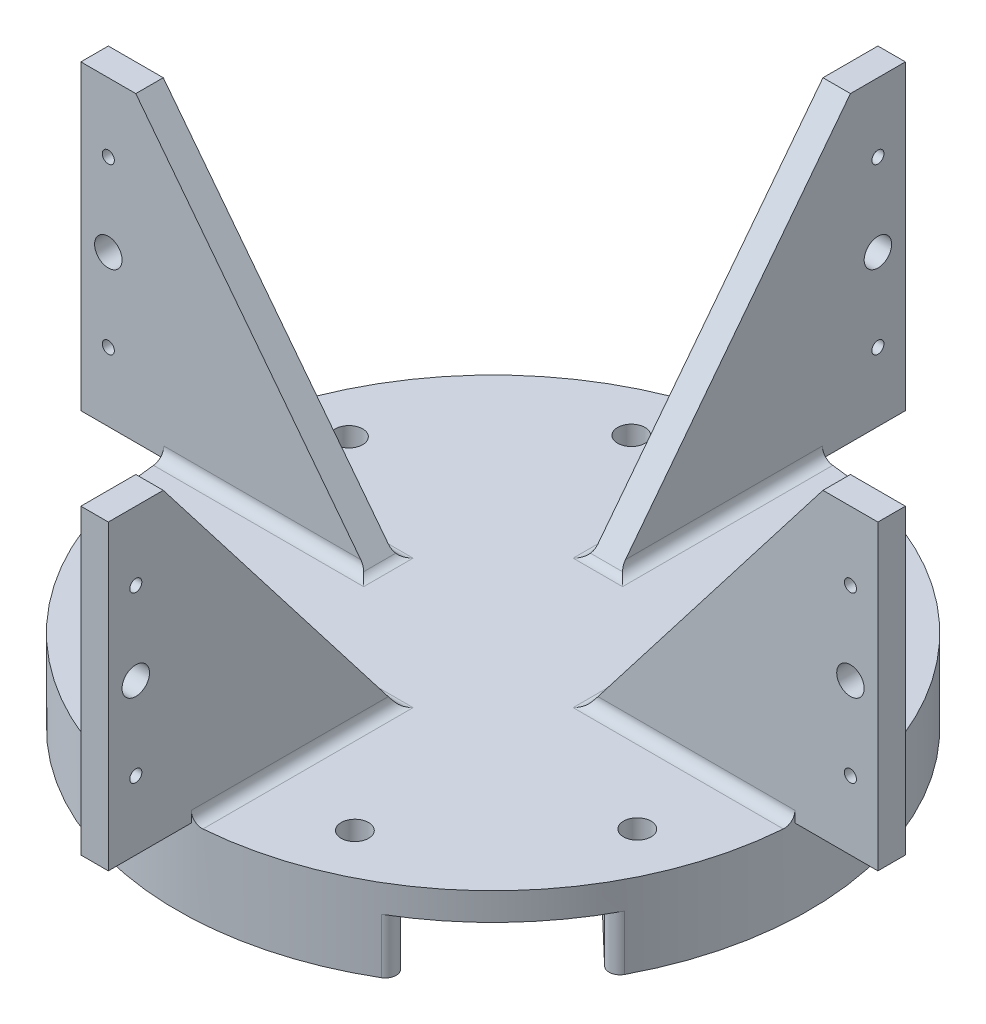
SolidWorks part; units mm, degrees
material "6061-T6 (SS)"
ref_plane "Front Plane" through (0, 0, 0) normal (0, 0, 1) x (1, 0, 0)
ref_plane "Top Plane" through (0, 0, 0) normal (0, 1, 0) x (1, 0, 0)
ref_plane "Right Plane" through (0, 0, 0) normal (1, 0, 0) x (0, 0, -1)
sketch "Sketch1" plane through (0, 0, 0) normal (0, 1, 0) x (1, 0, 0)
  circle A0 centre (0, 0) radius 73.025
  dimension "D1" = 146.05
extrude "Boss-Extrude1" add sketch "Sketch1" against normal blind 19.05
sketch "Sketch2" plane through (0, -19.05, 0) normal (0, -1, 0) x (1, 0, 0)
  line L0 (-89.3415, 0) -> (112.2326, 0) construction
  line L3 (0, 0) -> (-66.358, 26.8104) construction
  line L4 (47.2652, 68.1915) -> (-59.2635, -33.5672)
  line L5 (-59.2635, -33.5672) -> (-36.2362, -57.6739)
  line L6 (-36.2362, -57.6739) -> (70.2925, 44.0848)
  line L7 (70.2925, 44.0848) -> (47.2652, 68.1915)
  line L8 (0, 0) -> (78.7293, 75.2041) construction
  circle A0 centre (-57.8383, 23.3682) radius 3.175 construction
  circle A1 centre (-23.4231, 57.002) radius 3.175 construction
  circle A2 centre (24.6948, 56.4495) radius 3.175 construction
  circle A3 centre (58.3287, 22.0343) radius 3.175 construction
  circle A4 centre (57.7761, -26.0837) radius 3.175 construction
  circle A5 centre (23.3609, -59.7175) radius 3.175 construction
  circle A6 centre (-24.757, -59.165) radius 3.175 construction
  circle A7 centre (-58.3909, -24.7497) radius 3.175 construction
  circle A8 centre (0, 0) radius 73.025 construction
  point P23 (-0.0311, -1.3577)
  point P24 (39.9029, 61.1589)
  dimension "D2" = 6.35
  dimension "D7" = 16.6751
  dimension "D1" = 22
  dimension "D3" = 8
  dimension "D4" = 33.3375
  dimension "D5" = 147.32
  dimension "D6" = 66.04
extrude "Cut-Extrude1" cut sketch "Sketch2" against normal blind 12.7
sketch "Sketch3" plane through (0, 0, 0) normal (0, 1, 0) x (1, 0, 0)
  line L0 (0, 101.4749) -> (0, -101.4749) construction
  line L1 (-101.4749, 0) -> (101.4749, 0) construction
  line L2 (0, 0) -> (-105.9771, 42.8175) construction
  circle A0 centre (0, 0) radius 60.325 construction
  circle A2 centre (-55.9324, 22.5981) radius 3.175
  circle A3 centre (-23.5709, 55.5295) radius 3.175
  circle A4 centre (22.5981, 55.9324) radius 3.175
  circle A5 centre (55.5295, 23.5709) radius 3.175
  circle A6 centre (55.9324, -22.5981) radius 3.175
  circle A7 centre (23.5709, -55.5295) radius 3.175
  circle A8 centre (-22.5981, -55.9324) radius 3.175
  circle A9 centre (-55.5295, -23.5709) radius 3.175
  point P4 (0, 0)
  point P8 (0, 0)
  point P29 (0, 0)
  dimension "D1" = 22
  dimension "D2" = 8
  dimension "D3" = 120.65
  dimension "D4" = 6.35
extrude "Cut-Extrude2" cut sketch "Sketch3" against normal through all
sketch "Sketch6" plane through (0, 0, 0) normal (0, 0, 1) x (1, 0, 0)
  line L0 (-25.4607, 0) -> (-92.1357, 0)
  line L1 (73.025, 0) -> (-73.025, 0) construction
  line L2 (-92.1357, 0) -> (-92.1357, 69.85)
  line L3 (-92.1357, 69.85) -> (-79.4357, 69.85)
  line L4 (-79.4357, 69.85) -> (-25.4607, 0)
  line L5 (-73.025, 0) -> (-73.025, -19.05) construction
  line L6 (0, 34.925) -> (0, -28.7877) construction
  circle A0 centre (-85.7857, 53.975) radius 1.397
  circle A1 centre (-85.7857, 34.925) radius 3.175
  circle A2 centre (-85.7857, 15.875) radius 1.397
  point P5 (-73.025, 0)
  dimension "D5" = 2.794
  dimension "D6" = 2.794
  dimension "D7" = 6.35
  dimension "D8" = 38.1
  dimension "D1" = 66.675
  dimension "D2" = 69.85
  dimension "D3" = 12.7
  dimension "D4" = 19.1107
  dimension "D9" = 15.875
  dimension "D10" = 19.05
  dimension "D11" = 6.35
  dimension "D12" = 6.35
  dimension "D13" = 6.35
extrude "Boss-Extrude2" add sketch "Sketch6" along normal blind 3.175 and the other way blind 3.175
fillet "Fillet1" radius 7.62 2 edges at (-36.2362, -12.7, -57.6739) (-59.2635, -12.7, -33.5672)
fillet "Fillet2" radius 2.54 2 edges at (62.9281, -12.7, 37.0501) (39.9029, -12.7, 61.1589)
pattern_circular "CirPattern1" count 4 over 360 about axis through (0, -19.05, 0) along (0, 1, 0) of "Boss-Extrude2" reverse direction yes
sketch "Sketch8" plane through (0, 0, 0) normal (0, 1, 0) x (1, 0, 0)
  point P0 (0, 0)
fillet "Fillet3" radius 2.54 12 edges at (-49.2083, 0, 3.175) (-25.4607, 0, 0) (-49.2083, 0, -3.175) (3.175, 0, 49.2083) (0, 0, 25.4607) (-3.175, 0, 49.2083) (49.2083, 0, 3.175) (25.4607, 0, 0) (49.2083, 0, -3.175) (3.175, 0, -49.2083) (0, 0, -25.4607) (-3.175, 0, -49.2083)
